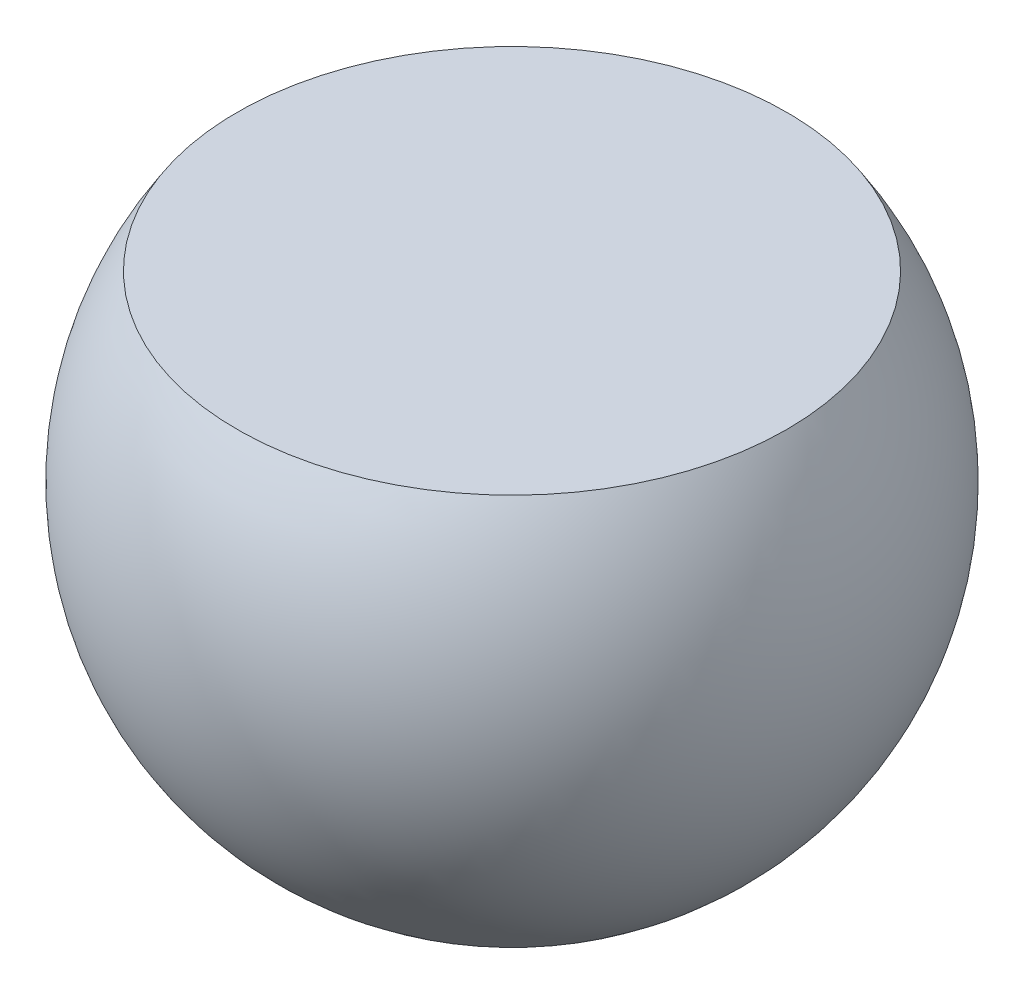
SolidWorks part; units mm, degrees
material "Polyethylene Cross-Linked"
ref_plane "Front Plane" through (0, 0, 0) normal (0, 0, 1) x (1, 0, 0)
ref_plane "Top Plane" through (0, 0, 0) normal (0, 1, 0) x (1, 0, 0)
ref_plane "Right Plane" through (0, 0, 0) normal (1, 0, 0) x (0, 0, -1)
other "Configuration Table"
sketch "Sketch1" plane through (0, 0, 0) normal (0, 0, 1) x (1, 0, 0)
  line L0 (0, 152.4) -> (0, -152.4)
  line L1 (0, 0) -> (152.4, 0) construction
  arc A0 (0, 152.4) -> (0, -152.4) centre (0, 0) cw
  point P2 (0, 0)
  dimension "D1" = 304.8
  dimension "D2" = 152.4
revolve "Revolve1" add sketch "Sketch1" angle 360 about L0
ref_plane "Plane1" through (0, 152.4, 0) normal (0, 1, 0) x (1, 0, 0)
sketch "Sketch2" plane through (0, 152.4, 0) normal (0, 1, 0) x (1, 0, 0)
  line L1 (-204.2456, -161.7613) -> (204.2456, -161.7613)
  line L2 (-204.2456, -161.7613) -> (-204.2456, 161.7613)
  line L3 (-204.2456, 161.7613) -> (204.2456, 161.7613)
  line L4 (204.2456, -161.7613) -> (204.2456, 161.7613)
  line L5 (-204.2456, -161.7613) -> (204.2456, 161.7613) construction
  line L6 (-204.2456, 161.7613) -> (204.2456, -161.7613) construction
  point P0 (0, 0)
extrude "Cut-Extrude1" cut sketch "Sketch2" against normal blind 68.1736
ref_plane "Plane2" through (0, -152.4, 0) normal (0, -1, 0) x (-1, 0, 0)
sketch "Sketch3" plane through (0, -152.4, 0) normal (0, -1, 0) x (-1, 0, 0)
  line L1 (-38.1, 38.1) -> (38.1, 38.1)
  line L2 (-38.1, 38.1) -> (-38.1, -38.1)
  line L3 (-38.1, -38.1) -> (38.1, -38.1)
  line L4 (38.1, 38.1) -> (38.1, -38.1)
  line L5 (-38.1, 38.1) -> (38.1, -38.1) construction
  line L6 (-38.1, -38.1) -> (38.1, 38.1) construction
  point P0 (0, 0)
  dimension "D1" = 76.2
  dimension "D2" = 76.2
extrude "Cut-Extrude2" cut sketch "Sketch3" against normal blind 38.1
sketch "Sketch5" plane through (0, -152.4, 0) normal (0, -1, 0) x (-1, 0, 0)
  line L1 (-196.6385, -180.9838) -> (196.6385, -180.9838)
  line L2 (-196.6385, -180.9838) -> (-196.6385, 180.9838)
  line L3 (-196.6385, 180.9838) -> (196.6385, 180.9838)
  line L4 (196.6385, -180.9838) -> (196.6385, 180.9838)
  line L5 (-196.6385, -180.9838) -> (196.6385, 180.9838) construction
  line L6 (-196.6385, 180.9838) -> (196.6385, -180.9838) construction
  point P0 (0, 0)
extrude "Cut-Extrude4" cut sketch "Sketch5" against normal blind 29.21
